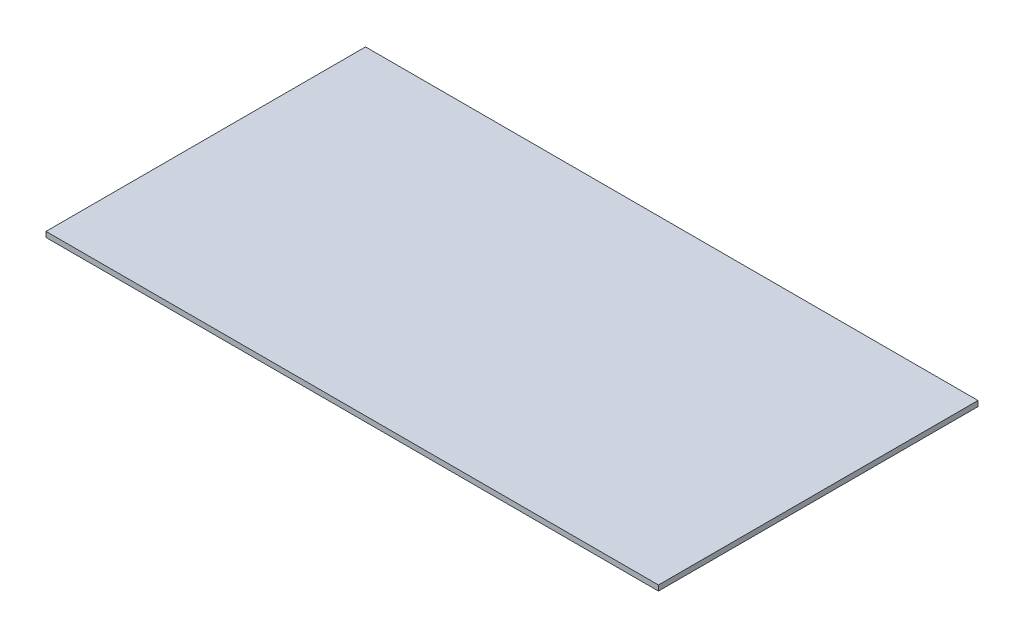
SolidWorks part; units mm, degrees
material "PC High Viscosity"
ref_plane "Front Plane" through (0, 0, 0) normal (0, 0, 1) x (1, 0, 0)
ref_plane "Top Plane" through (0, 0, 0) normal (0, 1, 0) x (1, 0, 0)
ref_plane "Right Plane" through (0, 0, 0) normal (1, 0, 0) x (0, 0, -1)
sketch "Sketch1" plane through (0, 0, 0) normal (0, 1, 0) x (1, 0, 0)
  line L1 (0, 0) -> (584.2, 0)
  line L2 (0, 0) -> (0, 304.8)
  line L3 (0, 304.8) -> (584.2, 304.8)
  line L4 (584.2, 0) -> (584.2, 304.8)
  dimension "D1" = 584.2
  dimension "D2" = 304.8
extrude "Boss-Extrude1" add sketch "Sketch1" along normal blind 5.08
sketch "Sketch2" plane through (0, 5.08, 0) normal (0, 1, 0) x (1, 0, 0)
  line L1 (50.8, 241.3) -> (228.6, 241.3)
  line L2 (50.8, 241.3) -> (50.8, 63.5)
  line L3 (50.8, 63.5) -> (228.6, 63.5)
  line L4 (228.6, 241.3) -> (228.6, 63.5)
  line L6 (584.2, 304.8) -> (0, 304.8) construction
  line L7 (0, 304.8) -> (0, 0) construction
  line L9 (254, 241.3) -> (431.8, 241.3)
  line L10 (254, 241.3) -> (254, 63.5)
  line L11 (254, 63.5) -> (431.8, 63.5)
  line L12 (431.8, 241.3) -> (431.8, 63.5)
  dimension "D1" = 177.8
  dimension "D2" = 177.8
  dimension "D3" = 63.5
  dimension "D4" = 50.8
  dimension "D5" = 177.8
  dimension "D6" = 177.8
  dimension "D7" = 25.4
  dimension "D8" = 63.5
